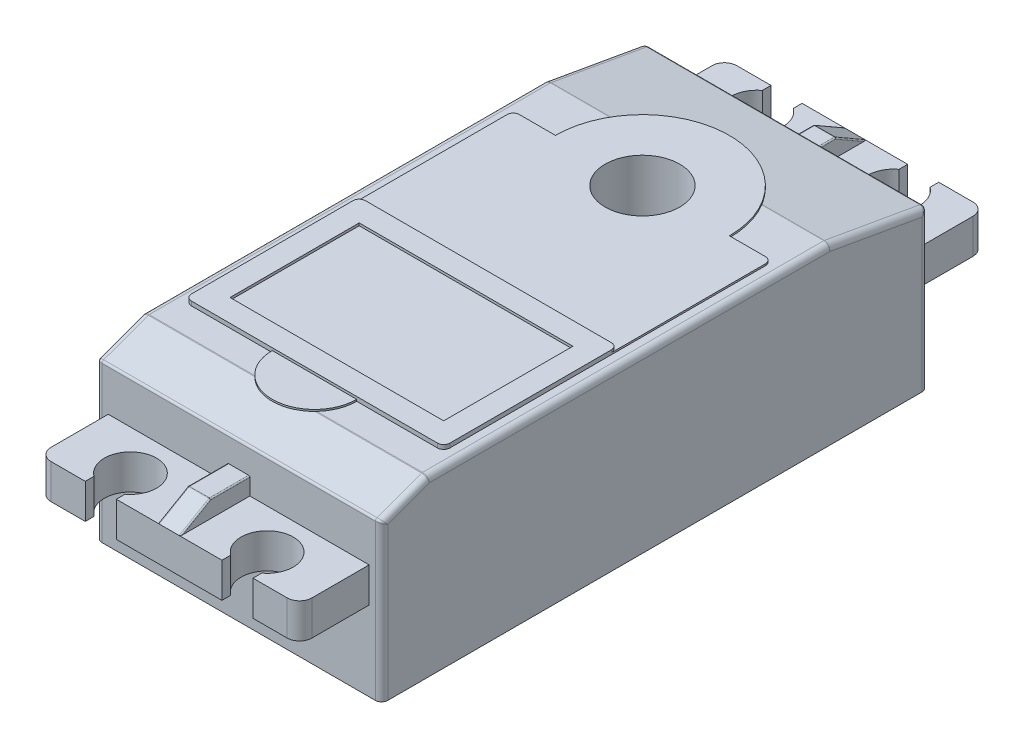
SolidWorks part; units mm, degrees
material "PC High Viscosity"
ref_plane "Front Plane" through (0, 0, 0) normal (0, 0, 1) x (1, 0, 0)
ref_plane "Top Plane" through (0, 0, 0) normal (0, 1, 0) x (1, 0, 0)
ref_plane "Right Plane" through (0, 0, 0) normal (1, 0, 0) x (0, 0, -1)
sketch "BaseS" plane through (0, 0, 0) normal (0, 1, 0) x (1, 0, 0)
  line L1 (-11.5, 22) -> (11.5, 22)
  line L2 (-11.5, 22) -> (-11.5, -22)
  line L3 (-11.5, -22) -> (11.5, -22)
  line L4 (11.5, 22) -> (11.5, -22)
  line L5 (-11.5, 22) -> (11.5, -22) construction
  line L6 (-11.5, -22) -> (11.5, 22) construction
  point P0 (0, 0)
  dimension "D1" = 23
  dimension "D2" = 44
extrude "BASE" add sketch "BaseS" along normal blind 14 contours L4 L3 L2 L1
sketch "ShaftHoleS" plane through (0, 14, 0) normal (0, 1, 0) x (1, 0, 0)
  line L0 (0, 10.5) -> (0, 22) construction
  line L1 (-11.5, 22) -> (11.5, 22) construction
  circle A0 centre (0, 10.5) radius 3
  dimension "D1" = 6
  dimension "D2" = 11.5
extrude "SHAFT HOLE" cut sketch "ShaftHoleS" against normal through all
sketch "Sketch1" plane through (0, 0, 0) normal (1, 0, 0) x (0, 0, -1)
  line L0 (-22, 12.6319) -> (-18.2412, 14)
  line L1 (-18.2412, 14) -> (-22, 14)
  line L2 (-22, 14) -> (-22, 12.6319)
  line L3 (14.1215, 14) -> (22, 14)
  line L4 (22, 14) -> (22, 12.6108)
  line L5 (22, 12.6108) -> (14.1215, 14)
  point P6 (-22.9284, 9.0039)
  point P8 (17.6884, 9)
  point P9 (25.5669, 9)
  dimension "D1" = 4
  dimension "D2" = 20
  dimension "D3" = 8
  dimension "D4" = 10
extrude "FRONT AND REAR CHAMFERS" cut sketch "Sketch1" against normal through all both and the other way through all
sketch "MountingTabS" plane through (0, 0, 22) normal (0, 0, 1) x (1, 0, 0)
  line L1 (-10.5, 9.2) -> (10.5, 9.2)
  line L2 (-10.5, 9.2) -> (-10.5, 6.4)
  line L3 (-10.5, 6.4) -> (10.5, 6.4)
  line L4 (10.5, 9.2) -> (10.5, 6.4)
  line L5 (-10.5, 9.2) -> (10.5, 6.4) construction
  line L6 (-10.5, 6.4) -> (10.5, 9.2) construction
  line L7 (11.5, 12.6319) -> (11.5, 0) construction
  line L8 (-11.5, 14) -> (11.5, 14) construction
  line L9 (0, 0) -> (0, 7.8) construction
  line L10 (-11.5, 0) -> (11.5, 0) construction
  point P0 (0, 7.8)
  dimension "D1" = 1
  dimension "D2" = 2.8
  dimension "D3" = 21
  dimension "D4" = 4.8
extrude "MOUNTING TAB" add sketch "MountingTabS" along normal blind 5.6
sketch "MountingHoleS" plane through (0, 9.2, 0) normal (0, 1, 0) x (1, 0, 0)
  line L0 (0, -27.6) -> (0, -22) construction
  line L1 (-6.75, -26.9) -> (-6.75, -27.6)
  line L2 (-6.75, -27.6) -> (-4.25, -27.6)
  line L3 (-4.25, -27.6) -> (-4.25, -26.9)
  line L4 (-5.5, -25.2125) -> (-5.5, -27.6) construction
  line L5 (10.5, -22) -> (-10.5, -22) construction
  line L6 (10.5, -27.6) -> (-10.5, -27.6) construction
  line L7 (-10.5, -27.6) -> (-10.5, -22) construction
  arc A0 (-4.25, -26.9) -> (-6.75, -26.9) centre (-5.5, -25.2125) ccw
  dimension "D1" = 4.2
  dimension "D2" = 5
  dimension "D3" = 2.5
  dimension "D4" = 0.7
extrude "MOUNTING HOLE" cut sketch "MountingHoleS" against normal through all
mirror "MH M" about plane through (0, 0, 0) normal (1, 0, 0) of "MOUNTING HOLE"
sketch "BottomAlignHoleS" plane through (0, 6.4, 0) normal (0, -1, 0) x (1, 0, 0)
  line L0 (0, 22) -> (0, 27.6) construction
  line L2 (-10.5, 22) -> (10.5, 22) construction
  line L3 (-4.25, 27.6) -> (4.25, 27.6) construction
  circle A0 centre (0, 24.8) radius 1.65
  point P8 (-0.1947, 25.1382)
  point P9 (0, 24.8)
  dimension "D1" = 3.3
extrude "BOTTOM ALIGN HOLE" cut sketch "BottomAlignHoleS" against normal blind 1.7
sketch "TriangularTabS" plane through (0, 0, 0) normal (1, 0, 0) x (0, 0, -1)
  line L0 (-22, 9.2) -> (-27.6, 9.2)
  line L2 (-22, 10.6) -> (-22, 9.2)
  line L3 (-26.9, 9.2) -> (-27.6, 9.2) construction
  line L4 (-27.6, 9.2) -> (-25.1751, 10.6)
  line L5 (-25.1751, 10.6) -> (-22, 10.6)
  dimension "D1" = 1.4
  dimension "D2" = 2.8
extrude "TRIANGULAR TAB" add sketch "TriangularTabS" along normal mid plane 1.8
mirror "MOUNTING TAB FEATURES M" about plane through (0, 0, 0) normal (0, 0, 1) of "TRIANGULAR TAB", "BOTTOM ALIGN HOLE", "MH M", "MOUNTING HOLE", "MOUNTING TAB"
sketch "BaseTopBodyS" plane through (0, 14, 0) normal (0, 1, 0) x (1, 0, 0)
  line L3 (0, -2.7) -> (0, 10.5) construction
  line L4 (10.4, -15.9) -> (3.4, -15.9)
  line L5 (10.4, -15.9) -> (10.4, 10.5)
  line L6 (10.4, 10.5) -> (7, 10.5)
  line L7 (-10.4, -15.9) -> (-10.4, 10.5)
  line L8 (10.4, -15.9) -> (-10.4, 10.5) construction
  line L9 (10.4, 10.5) -> (-10.4, -15.9) construction
  line L12 (0, -15.9) -> (0, -2.7) construction
  line L13 (-7, 10.5) -> (7, 10.5) construction
  line L14 (3.4, -15.9) -> (-3.4, -15.9) construction
  line L15 (-7, 10.5) -> (-10.4, 10.5)
  line L16 (-3.4, -15.9) -> (-10.4, -15.9)
  circle A2 centre (0, 10.5) radius 3 construction
  arc A3 (7, 10.5) -> (-7, 10.5) centre (0, 10.5) ccw
  circle A4 centre (0, 10.5) radius 3
  arc A5 (-3.4, -15.9) -> (3.4, -15.9) centre (0, -15.9) ccw
  point P3 (0, -2.7)
  point P9 (-10, 10.5)
  point P15 (16.8093, 7.6175)
  point P16 (16.6124, 5.9349)
  point P18 (-9.528, 10.5)
  point P19 (0, 8.7113)
  point P20 (0, 10.0652)
  dimension "D1" = 14
  dimension "D2" = 6.8
  dimension "D3" = 26.4
  dimension "D4" = 20.8
extrude "BASE TOP BODY" add sketch "BaseTopBodyS" along normal blind 0.14
fillet "BTB F" radius 0.5 4 edges at (-10.4, 14.07, -10.5) (10.4, 14.07, -10.5) (-10.4, 14.07, 15.9) (10.4, 14.07, 15.9)
sketch "TopBodyLabelNest" plane through (0, 14.14, 0) normal (0, 1, 0) x (1, 0, 0)
  line L4 (-10.4, 10) -> (-10.4, -15.4) construction
  line L5 (-9.9, -1.9) -> (9.9, -1.9)
  line L10 (-10.4, -2.4) -> (-10.4, -15.4)
  line L13 (10.4, -2.4) -> (10.4, -15.4)
  line L14 (10.4, -15.4) -> (10.4, 10) construction
  line L15 (-9.9, -15.9) -> (9.9, -15.9)
  arc A0 (9.9, -15.9) -> (10.4, -15.4) centre (9.9, -15.4) ccw construction
  arc A1 (-10.4, -15.4) -> (-9.9, -15.9) centre (-9.9, -15.4) ccw construction
  arc A2 (9.9, -15.9) -> (10.4, -15.4) centre (9.9, -15.4) ccw
  arc A3 (-10.4, -15.4) -> (-9.9, -15.9) centre (-9.9, -15.4) ccw
  arc A4 (10.4, -2.4) -> (9.9, -1.9) centre (9.9, -2.4) ccw
  arc A5 (-9.9, -1.9) -> (-10.4, -2.4) centre (-9.9, -2.4) ccw
  point P8 (10.4, -1.9)
  point P18 (-10.4, -1.9)
  dimension "D2" = 0.5
  dimension "D1" = 14
extrude "Sticker Holding Tab" add sketch "TopBodyLabelNest" along normal blind 0.2 thin thin type one direction reverse wall 1.8
fillet "MAIN BODY FEATURES F" radius 0.5 10 edges at (-11.5, 6.3054, -22) (11.5, 6.3054, -22) (-11.5, 6.316, 22) (11.5, 6.316, 22) (-11.5, 13.3054, -18.0608) (-11.5, 14, 2.0598) (-11.5, 13.316, 20.1206) (11.5, 13.3054, -18.0608) (11.5, 14, 2.0598) (11.5, 13.316, 20.1206)
fillet "SideTabsF" radius 1 4 edges at (-10.5, 7.8, -27.6) (10.5, 7.8, -27.6) (-10.5, 7.8, 27.6) (10.5, 7.8, 27.6)
fillet "TopChamfersF" radius 0.2 14 edges at (-11.3536, 12.4879, -21.8536) (11.3536, 12.4879, -21.8536) (-11.3536, 13.8536, -14.1087) (11.3536, 13.8536, -14.1087) (-11.3536, 13.8536, 18.2154) (11.3536, 13.8536, 18.2154) (-11.3536, 12.5294, 21.8536) (11.3536, 12.5294, 21.8536) (0, 12.6108, -22) (-8.4952, 14, -14.1215) (8.4952, 14, -14.1215) (-6.7327, 14, 18.2412) (6.7327, 14, 18.2412) (0, 12.6319, 22)
fillet "TT F" radius 0.1 10 edges at (-0.9, 10.6, 23.5876) (-0.9, 9.9, 26.3876) (0, 10.6, 25.1751) (0.9, 10.6, 23.5876) (0.9, 9.9, 26.3876) (-0.9, 9.9, -26.3876) (0.9, 9.9, -26.3876) (0, 10.6, -25.1751) (-0.9, 10.6, -23.5876) (0.9, 10.6, -23.5876)
